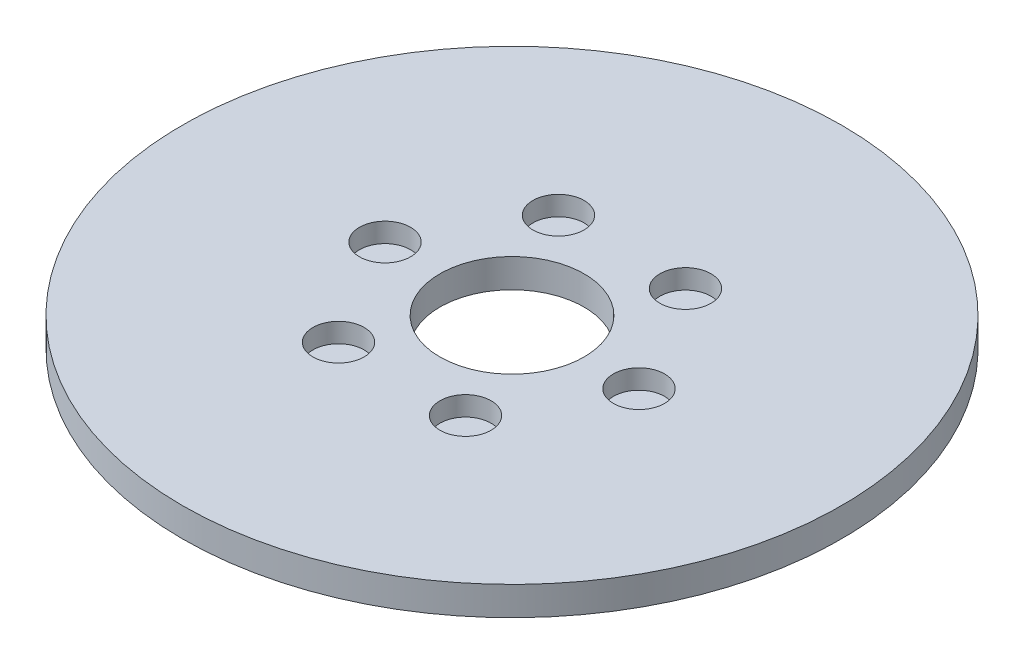
SolidWorks part; units mm, degrees
ref_plane "Front Plane" through (0, 0, 0) normal (0, 0, 1) x (1, 0, 0)
ref_plane "Top Plane" through (0, 0, 0) normal (0, 1, 0) x (1, 0, 0)
ref_plane "Right Plane" through (0, 0, 0) normal (1, 0, 0) x (0, 0, -1)
sketch "Sketch1" plane through (0, 0, 0) normal (0, 1, 0) x (1, 0, 0)
  circle A0 centre (0, 0) radius 80
  dimension "FLANGE_OD" = 160
extrude "Boss-Extrude1" add sketch "Sketch1" along normal blind 7
sketch "Sketch2" plane through (0, 0, 0) normal (0, 1, 0) x (1, 0, 0)
  circle A0 centre (0, 0) radius 17.5
  dimension "BORE_D" = 35
extrude "Cut-Extrude1" cut sketch "Sketch2" along normal through all
sketch "Sketch3" plane through (0, 7, 0) normal (0, 1, 0) x (1, 0, 0)
  circle A0 centre (0, 0) radius 30.8245 construction
  circle A1 centre (-30.8245, 0) radius 6.2137
  dimension "BOLT_D" = 12.4274
  dimension "BOLT_PCD" = 61.6491
extrude "Cut-Extrude2" cut sketch "Sketch3" against normal blind 4.7269
pattern_circular "CirPattern1" count 6 over 360 about axis through (0, 0, 0) along (0, 1, 0) of "Cut-Extrude2"
